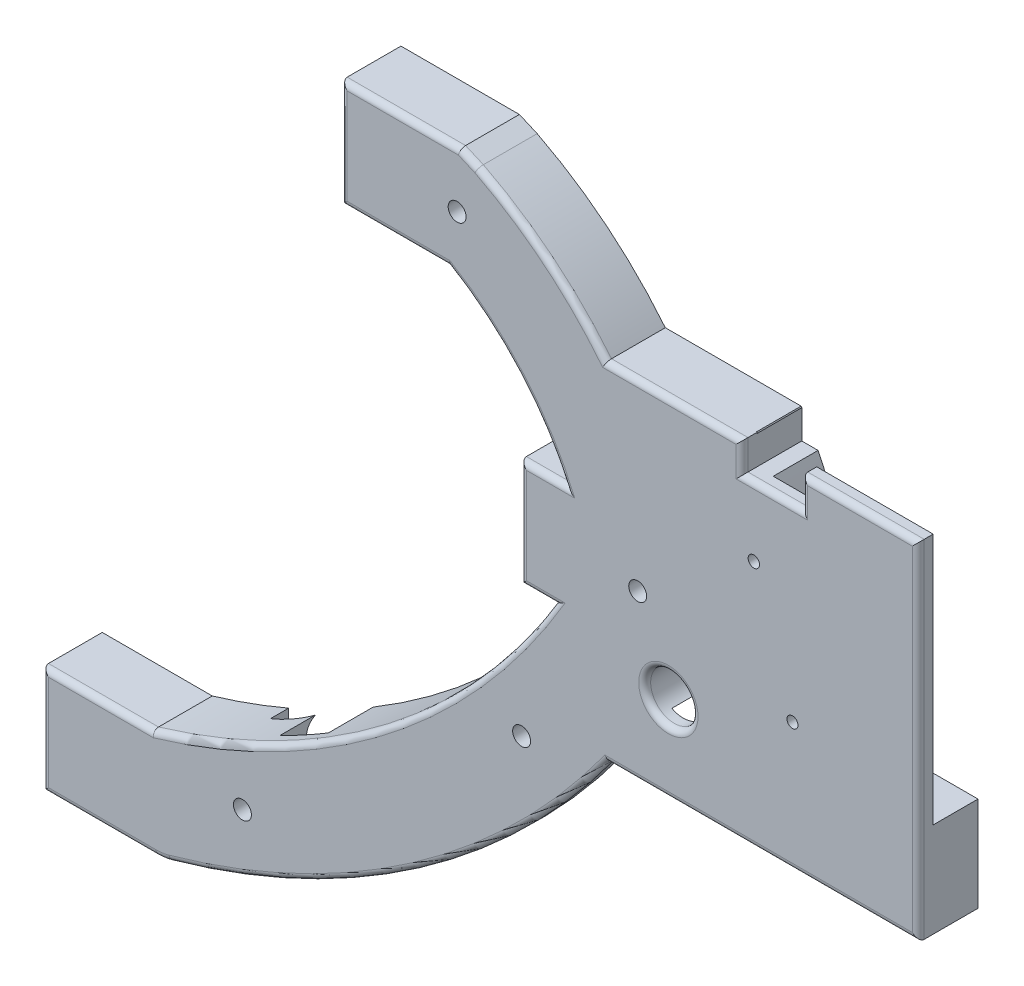
SolidWorks part; units mm, degrees
ref_plane "Front Plane" through (0, 0, 0) normal (0, 0, 1) x (1, 0, 0)
ref_plane "Top Plane" through (0, 0, 0) normal (0, 1, 0) x (1, 0, 0)
ref_plane "Right Plane" through (0, 0, 0) normal (1, 0, 0) x (0, 0, -1)
sketch "Sketch2" plane through (0, 0, 0) normal (0, 0, 1) x (1, 0, 0)
  line L4 (81.8886, 91.4585) -> (81.8886, 86.4585)
  line L5 (81.8886, 86.4585) -> (91.8886, 86.4585)
  line L6 (91.8886, 86.4585) -> (91.8886, 91.4585)
  line L7 (81.8886, 91.4585) -> (59.0461, 91.4585)
  line L8 (-35.2084, -17.8435) -> (-16.2062, -17.8435)
  line L9 (59.4454, 33.4585) -> (111.3886, 33.4585)
  line L10 (111.3886, 33.4585) -> (111.3886, 91.4585)
  line L11 (111.3886, 91.4585) -> (91.8886, 91.4585)
  line L12 (37.5976, 108.8698) -> (34.6185, 110.1565)
  line L13 (34.6185, 110.1565) -> (14.7916, 110.1565)
  line L14 (14.7916, 110.1565) -> (14.7916, 92.1565)
  line L15 (14.7916, 92.1565) -> (32.712, 92.1565)
  line L16 (52.3625, 70.1565) -> (44.7916, 70.1565)
  line L17 (44.7916, 70.1565) -> (44.7916, 52.1565)
  line L18 (44.7916, 52.1565) -> (50.5116, 52.1565)
  line L19 (-16.7871, 0.1565) -> (-35.2084, 0.1565)
  line L20 (-35.2084, 0.1565) -> (-35.2084, -17.8435)
  circle A7 centre (44.9916, 30.2255) radius 1.5
  circle A8 centre (64.4226, 60.9595) radius 1.5
  circle A9 centre (34.1966, 100.8375) radius 1.5
  circle A10 centre (83.8638, 74.9728) radius 0.9506
  circle A11 centre (90.3289, 54.9169) radius 0.9227
  circle A12 centre (-1.7444, -3.8105) radius 1.5
  circle A13 centre (69.5587, 47.8147) radius 3.9619
  arc A14 (-16.2062, -17.8435) -> (-13.7745, -17.5084) centre (-16.2113, -8.8162) ccw
  arc A20 (-13.7745, -17.5084) -> (59.4454, 33.4585) centre (-50.5576, 113.4128) ccw
  arc A21 (59.0461, 91.4585) -> (37.5976, 108.8698) centre (7.4405, 49.8034) ccw
  arc A22 (52.3625, 70.1565) -> (32.712, 92.1565) centre (7.4475, 49.8141) ccw
  arc A23 (-16.7871, 0.1565) -> (50.5116, 52.1565) centre (-50.5525, 113.405) ccw
  dimension "D2" = 5
  dimension "D3" = 19.5
  dimension "D1" = 10
extrude "Boss-Extrude1" add sketch "Sketch2" along normal blind 10
sketch "Sketch4" plane through (46, 0, 0) normal (-1, 0, 0) x (0, 0, 1)
  circle A0 centre (0.3059, 115.0899) radius 2.75
  dimension "D1" = 5.5
extrude "Cut-Extrude1" cut sketch "Sketch4" against normal blind 10 rebuild error yes
sketch "Sketch5" plane through (0, 0, 0) normal (0, 0, -1) x (-1, 0, 0)
  line L82 (-48, 119.9864) -> (-48, 122)
  line L83 (-48, 122) -> (-65.4134, 122)
  line L84 (-65.4134, 122) -> (-67.9535, 120.9029)
  line L85 (-89.2897, 103.302) -> (-111.097, 103.302)
  line L86 (-111.097, 103.302) -> (-111.097, 98.302)
  line L87 (-111.097, 98.302) -> (-125.097, 98.302)
  line L88 (-125.097, 98.302) -> (-125.097, 103.302)
  line L89 (-125.097, 103.302) -> (-140.597, 103.302)
  line L90 (-140.597, 103.302) -> (-140.597, 49.302)
  line L91 (-140.597, 49.302) -> (-89.6303, 49.302)
  line L92 (-15.0023, -2) -> (2, -2)
  line L93 (2, -2) -> (2, 0.6206)
  line L94 (2, 0.6206) -> (-2.012, 0.6206)
  line L95 (-2.012, 0.6206) -> (-2.012, 10.0044)
  line L96 (-2.012, 10.0044) -> (2, 10.0044)
  line L97 (2, 10.0044) -> (2, 12)
  line L98 (2, 12) -> (-14.7119, 12)
  line L99 (-85.2104, 68) -> (-78, 68)
  line L100 (-78, 68) -> (-78, 70.6195)
  line L101 (-78, 70.6195) -> (-81.955, 70.6195)
  line L102 (-81.955, 70.6195) -> (-81.955, 80.0034)
  line L103 (-81.955, 80.0034) -> (-78, 80.0034)
  line L104 (-78, 80.0034) -> (-78, 82)
  line L105 (-78, 82) -> (-86.5721, 82)
  line L106 (-64.4658, 108) -> (-48, 108)
  line L107 (-48, 108) -> (-48, 110.357)
  line L108 (-48, 110.357) -> (-53, 110.357)
  line L109 (-53, 110.357) -> (-53, 119.8229)
  line L110 (-53, 119.8229) -> (-51.923, 119.8229)
  line L111 (-51.923, 119.8229) -> (-51.923, 119.9864)
  line L112 (-51.923, 119.9864) -> (-48, 119.9864)
  line L113 (-48, 119.9864) -> (-48, 122)
  line L114 (-48, 122) -> (-65.4134, 122)
  line L115 (-65.4134, 122) -> (-67.9535, 120.9029)
  line L116 (-89.2897, 103.302) -> (-111.097, 103.302)
  line L117 (-111.097, 103.302) -> (-111.097, 98.302)
  line L118 (-111.097, 98.302) -> (-125.097, 98.302)
  line L119 (-125.097, 98.302) -> (-125.097, 103.302)
  line L120 (-125.097, 103.302) -> (-140.597, 103.302)
  line L121 (-140.597, 103.302) -> (-140.597, 49.302)
  line L122 (-140.597, 49.302) -> (-89.6303, 49.302)
  line L123 (-15.0023, -2) -> (2, -2)
  line L124 (2, -2) -> (2, 0.6206)
  line L125 (2, 0.6206) -> (-2.012, 0.6206)
  line L126 (-2.012, 0.6206) -> (-2.012, 10.0044)
  line L127 (-2.012, 10.0044) -> (2, 10.0044)
  line L128 (2, 10.0044) -> (2, 12)
  line L129 (2, 12) -> (-14.7119, 12)
  line L130 (-85.2104, 68) -> (-78, 68)
  line L131 (-78, 68) -> (-78, 70.6195)
  line L132 (-78, 70.6195) -> (-81.955, 70.6195)
  line L133 (-81.955, 70.6195) -> (-81.955, 80.0034)
  line L134 (-81.955, 80.0034) -> (-78, 80.0034)
  line L135 (-78, 80.0034) -> (-78, 82)
  line L136 (-78, 82) -> (-86.5721, 82)
  line L137 (-64.4658, 108) -> (-48, 108)
  line L138 (-48, 108) -> (-48, 110.357)
  line L139 (-48, 110.357) -> (-53, 110.357)
  line L140 (-53, 110.357) -> (-53, 119.8229)
  line L141 (-53, 119.8229) -> (-51.923, 119.8229)
  line L142 (-51.923, 119.8229) -> (-51.923, 119.9864)
  line L143 (-51.923, 119.9864) -> (-48, 119.9864)
  arc A10 (-67.9535, 120.9029) -> (-89.2897, 103.302) centre (-38.6489, 63.6469) ccw
  arc A11 (-89.6303, 49.302) -> (-16.8941, -1.7391) centre (19.3491, 127.2562) ccw
  arc A12 (-16.8941, -1.7391) -> (-15.0023, -2) centre (-14.9972, 5.0273) ccw
  arc A13 (-85.2104, 68) -> (-14.7119, 12) centre (19.3441, 127.2485) ccw
  arc A14 (-64.4658, 108) -> (-86.5721, 82) centre (-38.6559, 63.6576) ccw
  arc A15 (-67.9535, 120.9029) -> (-89.2897, 103.302) centre (-38.6489, 63.6469) ccw
  arc A16 (-89.6303, 49.302) -> (-16.8941, -1.7391) centre (19.3491, 127.2562) ccw
  arc A17 (-16.8941, -1.7391) -> (-15.0023, -2) centre (-14.9972, 5.0273) ccw
  arc A18 (-85.2104, 68) -> (-14.7119, 12) centre (19.3441, 127.2485) ccw
  arc A19 (-64.4658, 108) -> (-86.5721, 82) centre (-38.6559, 63.6576) ccw
  dimension "D1" = 2
extrude "Cut-Extrude2" cut sketch "Sketch5" against normal blind 7.5
sketch "Sketch6" plane through (76, 0, 0) normal (-1, 0, 0) x (0, 0, 1)
  circle A0 centre (0.3059, 75.1069) radius 2.75
  dimension "D1" = 5.5
extrude "Cut-Extrude3" cut sketch "Sketch6" against normal blind 6
sketch "Sketch7" plane through (-4, 0, 0) normal (-1, 0, 0) x (0, 0, 1)
  circle A0 centre (0.3059, 5.1079) radius 2.75
  dimension "D1" = 5.5
extrude "Cut-Extrude4" cut sketch "Sketch7" against normal blind 16
sketch "Sketch8" plane through (142.597, 0, 0) normal (1, 0, 0) x (0, 0, -1)
  line L0 (0, 47.302) -> (0, 105.302) construction
  line L1 (0, 79.302) -> (-4, 79.302)
  line L2 (0, 79.302) -> (0, 67.302)
  line L3 (0, 67.302) -> (-4, 67.302)
  line L4 (-4, 79.302) -> (-4, 67.302)
  line L5 (-10, 105.302) -> (0, 105.302) construction
  line L6 (-10, 47.302) -> (0, 47.302) construction
  dimension "D1" = 26
  dimension "D2" = 20
  dimension "D3" = 4
extrude "Cut-Extrude5" cut sketch "Sketch8" against normal blind 6 rebuild error yes
sketch "Sketch9" plane through (0, 86.4585, 0) normal (0, 1, 0) x (1, 0, 0)
  line L0 (113.097, 0) -> (123.097, 0)
  line L1 (123.097, 0) -> (123.097, -5)
  line L2 (91.8886, -10) -> (91.8886, -7.5) construction
  line L3 (123.097, -5) -> (113.097, -5)
  line L4 (81.8886, -10) -> (81.8886, 0) construction
  line L5 (113.097, -5) -> (113.097, 0)
  dimension "D1" = 5
extrude "Cut-Extrude6" cut sketch "Sketch9" against normal blind 6 rebuild error yes
fillet "Fillet1" radius 3 rebuild error yes
fillet "Fillet2" radius 1 rebuild error yes
fillet "Fillet4" radius 1 22 edges at (-25.7073, -17.8435, 10) (86.8886, 86.4585, 10) (81.8886, 88.9585, 10) (91.8886, 88.9585, 10) (-25.9978, 0.1565, 10) (21.7022, 19.8926, 10) (47.6516, 52.1565, 10) (44.7916, 61.1565, 10) (48.5771, 70.1565, 10) (44.221, 82.6605, 10) (23.7518, 92.1565, 10) (14.7916, 101.1565, 10) (24.705, 110.1565, 10) (36.1081, 109.5132, 10) (49.2385, 101.2934, 10) (70.4674, 91.4585, 10) (101.6386, 91.4585, 10) (111.3886, 62.4585, 10) (85.417, 33.4585, 10) (27.1338, 1.8001, 10) (-14.9789, -17.7589, 10) (-35.2084, -8.8435, 10)
fillet "Fillet5" radius 1 rebuild error yes
fillet "Fillet6" radius 1 1 edges at (73.5206, 47.8147, 10)
sketch "Sketch10" plane through (0, 0, 7.5) normal (0, 0, -1) x (-1, 0, 0)
  circle A0 centre (-64.4226, 60.9595) radius 3
  circle A1 centre (-64.4226, 60.9595) radius 1.5
  circle A2 centre (-44.9916, 30.2255) radius 1.5
  circle A3 centre (-44.9916, 30.2255) radius 3
  circle A4 centre (1.7444, -3.8105) radius 1.5
  circle A5 centre (1.7444, -3.8105) radius 3
  circle A6 centre (-34.1966, 100.8375) radius 3
  circle A7 centre (-34.1966, 100.8375) radius 1.5
  dimension "D1" = 6
  dimension "D2" = 3
  dimension "D3" = 3
  dimension "D4" = 6
  dimension "D5" = 6
  dimension "D6" = 3
  dimension "D7" = 6
  dimension "D8" = 3
extrude "Boss-Extrude2" add sketch "Sketch10" along normal blind 7
